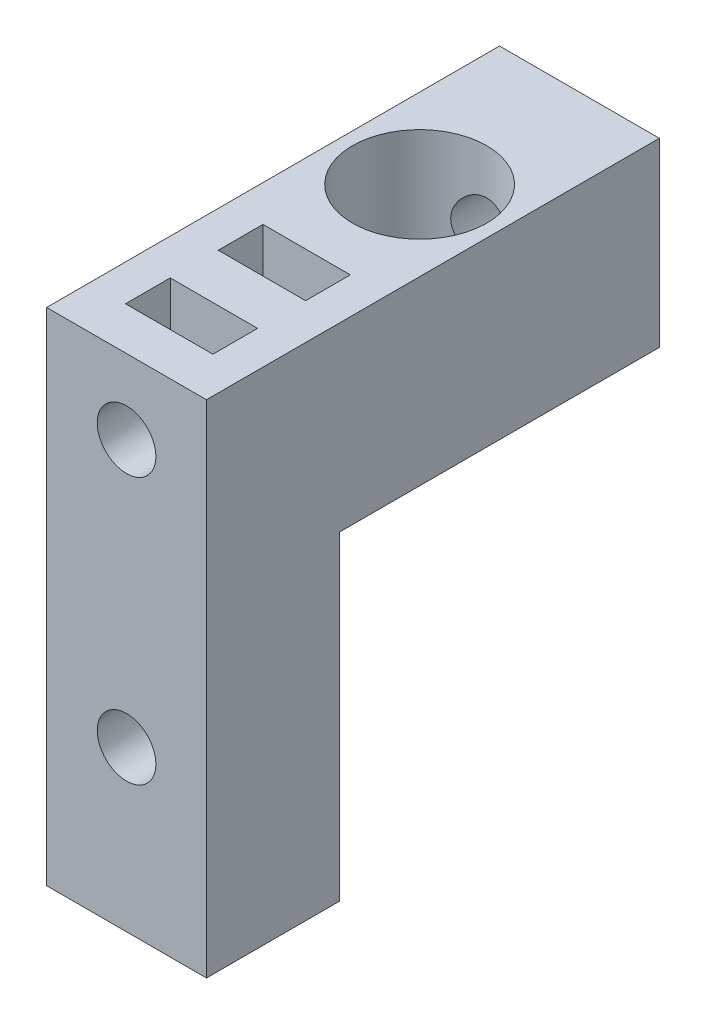
SolidWorks part; units mm, degrees
material "ABS PC"
ref_plane "Front Plane" through (0, 0, 0) normal (0, 0, 1) x (1, 0, 0)
ref_plane "Top Plane" through (0, 0, 0) normal (0, 1, 0) x (1, 0, 0)
ref_plane "Right Plane" through (0, 0, 0) normal (1, 0, 0) x (0, 0, -1)
sketch "Sketch1" plane through (0, 0, 0) normal (0, 0, 1) x (1, 0, 0)
  line L0 (0, 0) -> (15, 0)
  line L1 (0, 0) -> (0, 47)
  line L2 (15, 0) -> (15, 47)
  line L3 (0, 47) -> (15, 47)
  dimension "D1" = 47
  dimension "D2" = 15
extrude "Boss-Extrude1" add sketch "Sketch1" along normal blind 42.5
sketch "Sketch2" plane through (0, 0, 0) normal (-1, 0, 0) x (0, 0, 1)
  line L0 (0, 0) -> (0, 30)
  line L1 (0, 0) -> (30, 0)
  line L2 (0, 30) -> (30, 30)
  line L3 (30, 0) -> (30, 30)
  line L4 (0, 47) -> (0, 0) construction
  dimension "D1" = 30
  dimension "D2" = 30
extrude "Cut-Extrude1" cut sketch "Sketch2" against normal through all
sketch "Sketch3" plane through (0, 0, 42.5) normal (0, 0, 1) x (1, 0, 0)
  line L0 (0, 47) -> (0, 0) construction
  line L1 (0, 0) -> (15, 0) construction
  line L2 (15, 47) -> (0, 47) construction
  circle A0 centre (7.5, 15) radius 2.75
  circle A1 centre (7.5, 40) radius 2.75
  dimension "D1" = 5.5
  dimension "D2" = 5.5
  dimension "D4" = 15
  dimension "D5" = 7
  dimension "D3" = 7.5
extrude "Cut-Extrude2" cut sketch "Sketch3" against normal blind 15
sketch "Sketch4" plane through (0, 47, 0) normal (0, 1, 0) x (1, 0, 0)
  line L0 (0, -42.5) -> (0, 0) construction
  line L1 (15, 0) -> (0, 0) construction
  circle A0 centre (7.5, -15) radius 3.25
  dimension "D1" = 6.5
  dimension "D2" = 7.5
  dimension "D3" = 15
extrude "Cut-Extrude3" cut sketch "Sketch4" against normal up to next
sketch "Sketch5" plane through (0, 0, 27.5) normal (0, 0, 1) x (1, 0, 0)
  circle A0 centre (7.5, 40) radius 2.75
  circle A1 centre (7.5, 40) radius 2.75 construction
  dimension "D1" = 5.5
extrude "Cut-Extrude4" cut sketch "Sketch5" against normal through all
sketch "Sketch6" plane through (0, 30, 0) normal (0, -1, 0) x (1, 0, 0)
  circle A0 centre (7.5, 15) radius 6.3
  circle A1 centre (7.5, 15) radius 3.25 construction
  dimension "D1" = 12.6
extrude "Cut-Extrude6" cut sketch "Sketch6" against normal blind 15 from offset 7.2 offset against normal yes
hole_wizard "CSK for M6 Flat Head Machine Screw1" positions "Sketch8" profile "Sketch7" countersink size "M6" standard "ANSI Metric" end condition through all
sketch "Sketch8" plane through (0, 37.2, 0) normal (0, 1, 0) x (1, 0, 0)
  point P0 (7.5, -15)
sketch "Sketch7" plane through (7.5, 37.2, 15) normal (1, 0, 0) x (0, 0, 1)
  line L0 (0, 0) -> (0, 37.2)
  line L1 (0, 37.2) -> (3.3, 37.2)
  line L2 (3.3, 37.2) -> (3.3, 3)
  line L3 (3.3, 3) -> (6.3, 0)
  line L5 (6.3, 0) -> (0, 0)
  line L6 (-3.3, 3) -> (-6.3, 0) construction
  line L11 (0, -6.35) -> (0, 107.95) construction
  dimension "Thru Hole Dia." = 6.6
  dimension "Thru Hole Depth" = 37.2
  dimension "Near C'Sink Dia." = 12.6
  dimension "Near C'Sink Angle" = 90
sketch "Sketch10" plane through (0, 47, 0) normal (0, 1, 0) x (1, 0, 0)
  line L0 (3.4, -38.5) -> (11.6, -38.5)
  line L1 (3.4, -38.5) -> (3.4, -34.3)
  line L2 (11.6, -38.5) -> (11.6, -34.3)
  line L3 (3.4, -34.3) -> (11.6, -34.3)
  line L4 (3.4, -29.8) -> (11.6, -29.8)
  line L5 (3.4, -29.8) -> (3.4, -25.6)
  line L6 (11.6, -29.8) -> (11.6, -25.6)
  line L7 (3.4, -25.6) -> (11.6, -25.6)
  line L8 (0, -42.5) -> (0, 0) construction
  line L9 (15, -42.5) -> (0, -42.5) construction
  dimension "D1" = 4.2
  dimension "D2" = 8.2
  dimension "D3" = 3.4
  dimension "D4" = 4
  dimension "D5" = 4.5
extrude "Cut-Extrude7" cut sketch "Sketch10" against normal blind 12
